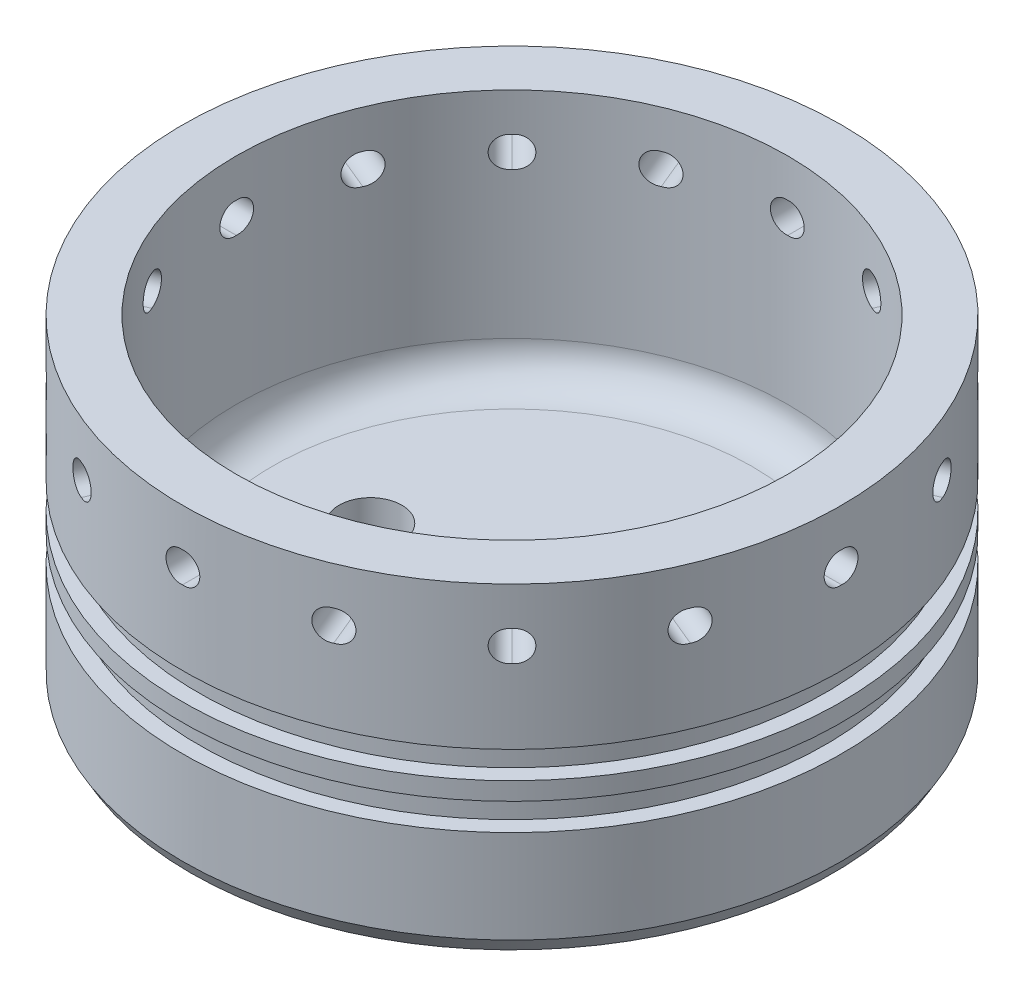
SolidWorks part; units mm, degrees
material "6061-T6 (SS)"
ref_plane "Front Plane" through (0, 0, 0) normal (0, 0, 1) x (1, 0, 0)
ref_plane "Top Plane" through (0, 0, 0) normal (0, 1, 0) x (1, 0, 0)
ref_plane "Right Plane" through (0, 0, 0) normal (1, 0, 0) x (0, 0, -1)
sketch "Sketch1" plane through (0, 0, 0) normal (0, 0, 1) x (1, 0, 0)
  line L1 (0, -9.525) -> (58.4454, -9.525)
  line L2 (58.4454, -9.525) -> (58.4454, 41.275) construction
  line L3 (0, 47.7012) -> (9.525, 47.7012)
  line L4 (58.4454, -9.525) -> (58.4454, 3.175)
  line L5 (58.4454, 3.175) -> (9.525, 3.175)
  line L6 (9.525, 3.175) -> (9.525, 47.7012)
  line L8 (0, -9.525) -> (0, 9.525)
  line L9 (0, 9.525) -> (2.8194, 9.525)
  line L10 (2.8194, 9.525) -> (2.8194, 14.3256)
  line L11 (2.8194, 14.3256) -> (0, 14.3256)
  line L15 (0, 14.3256) -> (0, 17.5006)
  line L16 (0, 17.5006) -> (2.8194, 17.5006)
  line L17 (2.8194, 17.5006) -> (2.8194, 22.3012)
  line L18 (2.8194, 22.3012) -> (0, 22.3012)
  line L19 (0, 22.3012) -> (0, 47.7012)
  dimension "D1" = 3.175
  dimension "D2" = 58.4454
  dimension "D3" = 12.7
  dimension "D4" = 19.05
  dimension "D5" = 4.8006
  dimension "D6" = 2.8194
  dimension "D7" = 3.175
  dimension "D10" = 25.4
  dimension "D11" = 9.525
revolve "Revolve1" add sketch "Sketch1" angle 360 about L2 region at (0.818, 0, 0)
ref_plane "HoleReferencePlane" through (0, 0, 58.4454) normal (0, 0, 1) x (1, 0, 0)
sketch "HoleReferencePoint" plane through (0, 0, 58.4454) normal (0, 0, 1) x (1, 0, 0)
  line L0 (107.3658, 47.7012) -> (9.525, 47.7012) construction
  point P0 (58.7375, 38.1762)
  dimension "D1" = 9.525
hole_wizard "ForwardClosureHoles" positions "Sketch3" profile "Sketch5" hole size "1/4-28" standard "ANSI Inch" end condition through all
sketch "Sketch3" plane through (0, 0, 58.4454) normal (0, 0, 1) x (1, 0, 0)
  point P0 (58.7375, 38.1762)
sketch "Sketch5" plane through (58.7375, 38.1762, 58.4454) normal (1, 0, 0) x (0, -1, 0)
  line L0 (0, 0) -> (0, 116.8908)
  line L1 (0, 116.8908) -> (2.7051, 116.8908)
  line L2 (2.7051, 116.8908) -> (2.7051, 0)
  line L5 (2.7051, 0) -> (0, 0)
  line L11 (0, -6.35) -> (0, 107.95) construction
  dimension "Thru Hole Dia." = 5.4102
  dimension "Thru Hole Depth" = 116.8908
sketch "Centerline" plane through (0, 0, 0) normal (0, 0, 1) x (1, 0, 0)
  line L0 (58.4454, 47.7012) -> (58.4454, -9.525) construction
  line L1 (116.8908, 47.7012) -> (0, 47.7012) construction
  line L2 (0, -9.525) -> (116.8908, -9.525) construction
pattern_circular "HolePattern" count 16 over 360 about axis through (58.4454, 47.7012, 0) along (0, -1, 0) of "ForwardClosureHoles"
ref_plane "HoleAlignmentPlane" through (0, 38.1762, 0) normal (0, 1, 0) x (1, 0, 0)
chamfer "Chamfer1" distance 2.54 angle 30 1 edges at (58.4454, -9.525, -58.4454) first distance on face at (58.4454, 9.525, -58.4454)
fillet "Fillet1" radius 6.35 1 edges at (58.4454, 3.175, -48.9204)
sketch "Sketch7" plane through (0, 0, 0) normal (0, 1, 0) x (1, 0, 0)
  line L0 (58.7375, 0) -> (84.1375, 0)
  line L2 (58.7375, 0) -> (33.3375, 0)
  point P4 (33.3375, 0)
  point P5 (58.7375, 0)
  dimension "D1" = 25.4
  dimension "D2" = 25.4
  dimension "D3" = 33.3375
hole_wizard "Pipe Tap Drill for 1/8 Tap1" positions "Sketch8" profile "Sketch9" hole size "1/8" standard "ANSI Inch" end condition through all
sketch "Sketch8" plane through (0, 3.175, 0) normal (0, 1, 0) x (1, 0, 0)
  point P0 (58.7375, 0)
sketch "Sketch9" plane through (58.7375, 3.175, 0) normal (1, 0, 0) x (0, 0, 1)
  line L0 (0, 0) -> (0, 12.7)
  line L1 (0, 12.7) -> (4.2164, 12.7)
  line L2 (4.2164, 12.7) -> (4.2164, 0)
  line L5 (4.2164, 0) -> (0, 0)
  line L11 (0, -6.35) -> (0, 107.95) construction
  dimension "Thru Hole Dia." = 8.4328
  dimension "Thru Hole Depth" = 12.7
hole_wizard "Pipe Tap Drill for 1/4 Tap1" positions "Sketch13" profile "Sketch14" hole size "1/4" standard "ANSI Inch" end condition through all
sketch "Sketch13" plane through (0, 3.175, 0) normal (0, 1, 0) x (1, 0, 0)
  point P0 (33.3375, 0)
sketch "Sketch14" plane through (33.3375, 3.175, 0) normal (1, 0, 0) x (0, 0, 1)
  line L0 (0, 0) -> (0, 12.7)
  line L1 (0, 12.7) -> (5.5626, 12.7)
  line L2 (5.5626, 12.7) -> (5.5626, 0)
  line L5 (5.5626, 0) -> (0, 0)
  line L11 (0, -6.35) -> (0, 107.95) construction
  dimension "Thru Hole Dia." = 11.1252
  dimension "Thru Hole Depth" = 12.7
